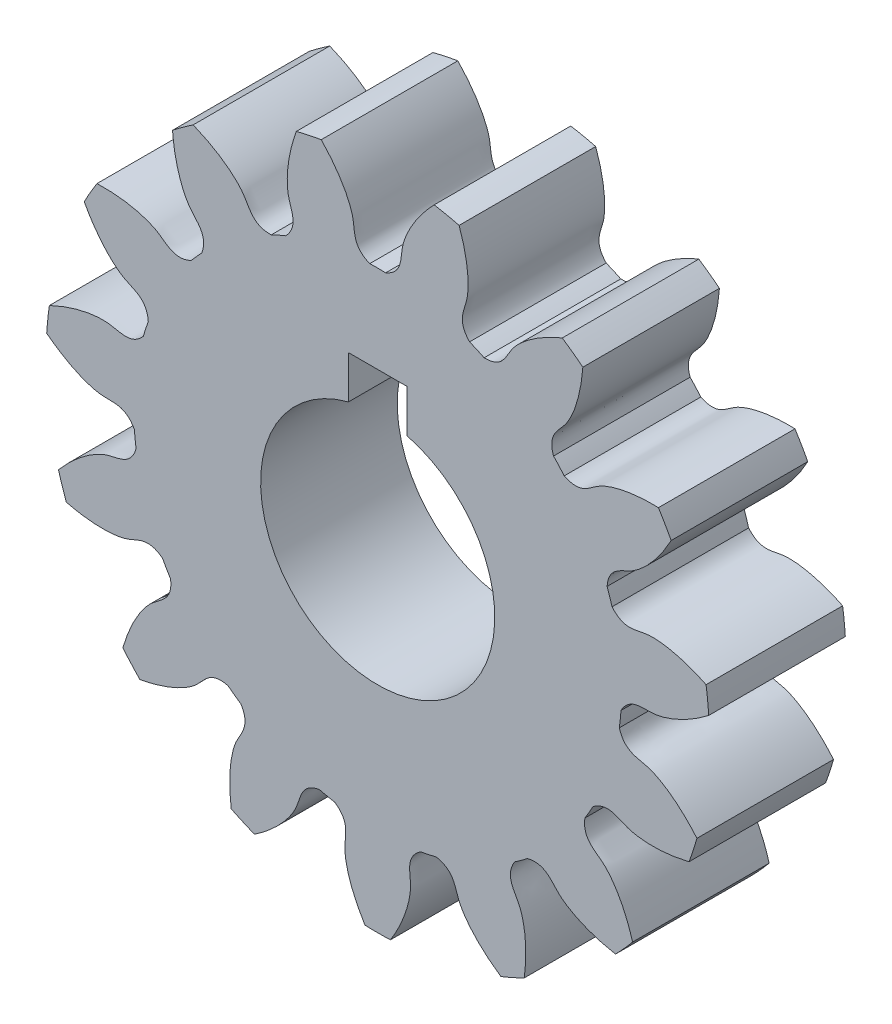
SolidWorks part; units mm, degrees
ref_plane "前视基准面" through (0, 0, 0) normal (0, 0, 1) x (1, 0, 0)
ref_plane "上视基准面" through (0, 0, 0) normal (0, 1, 0) x (1, 0, 0)
ref_plane "右视基准面" through (0, 0, 0) normal (1, 0, 0) x (0, 0, -1)
sketch "草图1" plane through (0, 0, 0) normal (0, 0, 1) x (1, 0, 0)
  circle A0 centre (0, 0) radius 17
extrude "凸台-拉伸1" add sketch "草图1" along normal blind 7
ref_axis "基准轴1" through (0, 0, -0.5) along (0, 0, 1)
sketch "草图2" plane through (0, 0, 0) normal (0, 0, 1) x (1, 0, 0)
  line L0 (0, 0) -> (0, 17) construction
  circle A0 centre (0, 0) radius 17 construction
  arc A1 (0.4086, 12.4933) -> (-0.4086, 12.4933) centre (0, 0) ccw
  arc A2 (6.4937, 19.2719) -> (-6.4937, 19.2719) centre (0, 0) ccw
  spline S0 degree 3 poles (0.4086, 12.4933) (1.3144, 12.8688) (1.1442, 13.5727) (1.3025, 14.217) (1.3149, 14.2633) (1.3297, 14.3148) (1.3472, 14.3713) (1.3676, 14.4329) (1.3912, 14.4993) (1.418, 14.5705) (1.4484, 14.6465) (1.4824, 14.7269) (1.5204, 14.8119) (1.5624, 14.9011) (1.6088, 14.9946) (1.6596, 15.0921) (1.715, 15.1935) (1.7753, 15.2987) (1.8405, 15.4075) (1.9109, 15.5198) (1.9867, 15.6353) (2.0679, 15.754) (2.1547, 15.8755) (2.2473, 15.9999) (2.3459, 16.1268) (2.4505, 16.2561) (2.5613, 16.3877) (2.6784, 16.5212) (2.802, 16.6565) (2.9322, 16.7934) (3.069, 16.9316) (3.2126, 17.0711) (3.3631, 17.2115) (3.5206, 17.3526) (3.6851, 17.4942) (3.8568, 17.6361) (4.0357, 17.778) (4.2219, 17.9197) (4.4154, 18.061) (4.6163, 18.2017) (4.8247, 18.3414) (5.0406, 18.48) (5.2641, 18.6172) (5.4951, 18.7527) (5.7336, 18.8864) (6.0652, 19.0635) (6.3203, 19.1901) (6.4937, 19.2719) knots 0 0 0 0 0.202473 0.206979 0.212085 0.217793 0.224101 0.23101 0.23852 0.24663 0.255341 0.264653 0.274566 0.285079 0.296194 0.307909 0.320225 0.333141 0.346659 0.360777 0.375496 0.390816 0.406736 0.423257 0.440379 0.458102 0.476426 0.49535 0.514875 0.535001 0.555728 0.577055 0.598984 0.621513 0.644642 0.668373 0.692704 0.717636 0.743169 0.769303 0.796037 0.823373 0.851309 0.879845 0.908983 0.938721 1 1 1 1
  spline S1 degree 3 poles (-0.4086, 12.4933) (-1.3144, 12.8688) (-1.1442, 13.5727) (-1.3025, 14.217) (-1.3149, 14.2633) (-1.3297, 14.3148) (-1.3472, 14.3713) (-1.3676, 14.4329) (-1.3912, 14.4993) (-1.418, 14.5705) (-1.4484, 14.6465) (-1.4824, 14.7269) (-1.5204, 14.8119) (-1.5624, 14.9011) (-1.6088, 14.9946) (-1.6596, 15.0921) (-1.715, 15.1935) (-1.7753, 15.2987) (-1.8405, 15.4075) (-1.9109, 15.5198) (-1.9867, 15.6353) (-2.0679, 15.754) (-2.1547, 15.8755) (-2.2473, 15.9999) (-2.3459, 16.1268) (-2.4505, 16.2561) (-2.5613, 16.3877) (-2.6784, 16.5212) (-2.802, 16.6565) (-2.9322, 16.7934) (-3.069, 16.9316) (-3.2126, 17.0711) (-3.3631, 17.2115) (-3.5206, 17.3526) (-3.6851, 17.4942) (-3.8568, 17.6361) (-4.0357, 17.778) (-4.2219, 17.9197) (-4.4154, 18.061) (-4.6163, 18.2017) (-4.8247, 18.3414) (-5.0406, 18.48) (-5.2641, 18.6172) (-5.4951, 18.7527) (-5.7336, 18.8864) (-6.0652, 19.0635) (-6.3203, 19.1901) (-6.4937, 19.2719) knots 0 0 0 0 0.202473 0.206979 0.212085 0.217793 0.224101 0.23101 0.23852 0.24663 0.255341 0.264653 0.274566 0.285079 0.296194 0.307909 0.320225 0.333141 0.346659 0.360777 0.375496 0.390816 0.406736 0.423257 0.440379 0.458102 0.476426 0.49535 0.514875 0.535001 0.555728 0.577055 0.598984 0.621513 0.644642 0.668373 0.692704 0.717636 0.743169 0.769303 0.796037 0.823373 0.851309 0.879845 0.908983 0.938721 1 1 1 1
extrude "切除-拉伸1" cut sketch "草图2" along normal through all
pattern_circular "阵列(圆周)1" count 15 every 24 about axis through (0, 0, -0.5) along (0, 0, 1) of "切除-拉伸1"
sketch "草图3" plane through (0, 0, 0) normal (0, 0, 1) x (1, 0, 0)
  circle A0 centre (0, 0) radius 15 construction
  dimension "Dn" = 30
sketch "草图4" plane through (0, 0, 7) normal (0, 0, 1) x (1, 0, 0)
  line L0 (-1.5, 4) -> (-1.5, 5.8095) construction
  line L1 (-1.5, 4) -> (1.5, 4) construction
  line L2 (-1.5, 5.8095) -> (-1.5, 8)
  line L3 (-1.5, 8) -> (1.5, 8)
  line L4 (1.5, 5.8095) -> (1.5, 8)
  line L5 (-1.5, 4) -> (1.5, 8) construction
  line L6 (-1.5, 8) -> (1.5, 4) construction
  line L7 (1.5, 4) -> (1.5, 5.8095) construction
  arc A0 (-1.5, 5.8095) -> (1.5, 5.8095) centre (0, 0) ccw
  arc A1 (1.5, 5.8095) -> (0, 6) centre (0, 0) ccw construction
  arc A2 (0, 6) -> (-1.5, 5.8095) centre (0, 0) ccw construction
  point P3 (0, 6)
  dimension "D1" = 12
  dimension "D2" = 3
  dimension "D3" = 4
extrude "切除-拉伸2" cut sketch "草图4" against normal blind 10
